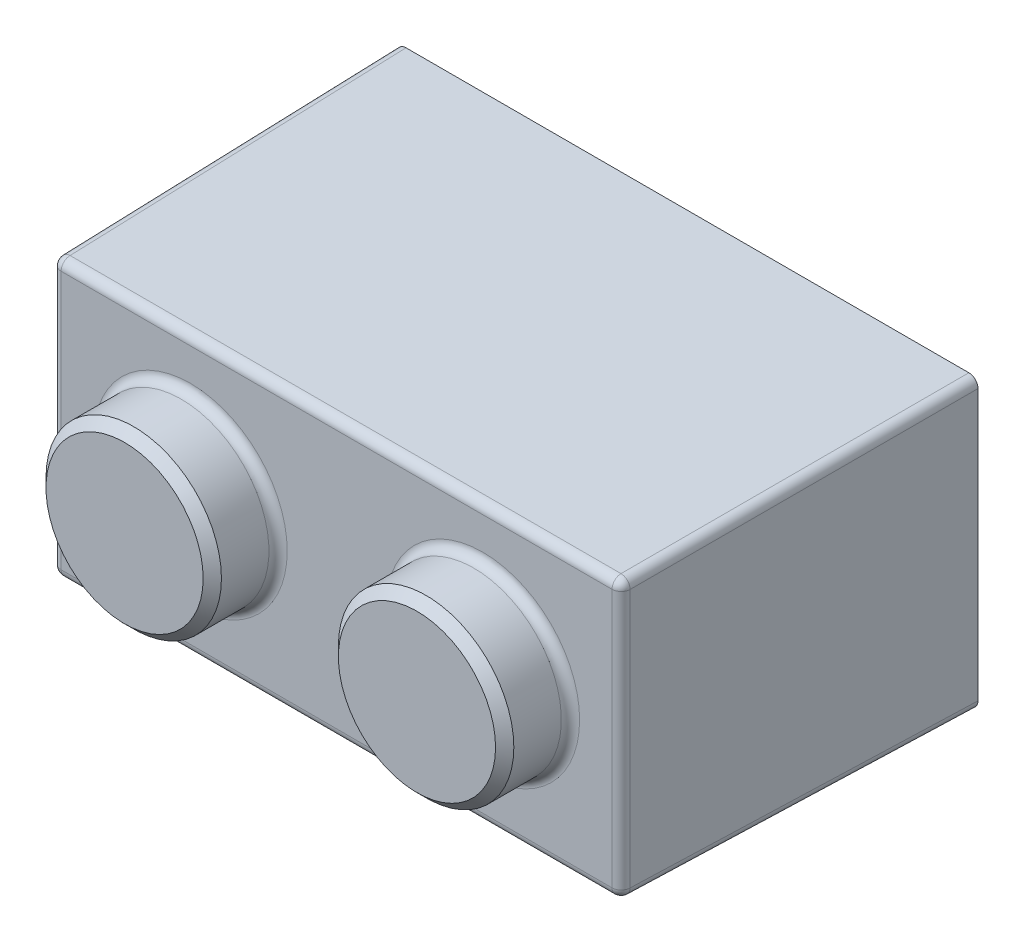
SolidWorks part; units mm, degrees
material "ABS"
ref_plane "Front" through (0, 0, 0) normal (0, 0, 1) x (1, 0, 0)
ref_plane "Top" through (0, 0, 0) normal (0, 1, 0) x (1, 0, 0)
ref_plane "Right" through (0, 0, 0) normal (1, 0, 0) x (0, 0, -1)
sketch "Sketch1" plane through (0, 0, 0) normal (0, 0, 1) x (1, 0, 0)
  line L1 (0, 0) -> (15.9, 0)
  line L2 (0, 0) -> (0, 7.9)
  line L3 (0, 7.9) -> (15.9, 7.9)
  line L4 (15.9, 0) -> (15.9, 7.9)
  dimension "D1" = 15.9
  dimension "D2" = 7.9
extrude "Main Body" add sketch "Sketch1" along normal blind 9.6 draft 1
sketch "Sketch2" plane through (0, 0, 9.6) normal (0, 0, 1) x (1, 0, 0)
  line L1 (0, 7.9) -> (0, 0) construction
  line L2 (0, 0) -> (15.9, 0) construction
  circle A0 centre (3.95, 3.95) radius 2.4
  dimension "D3" = 4.8
  dimension "D1" = 3.95
  dimension "D2" = 3.95
extrude "Post" add sketch "Sketch2" along normal blind 1.8
pattern_linear "Post LPattern1" count 2 spacing 8 along (1, 0, 0) of "Post"
shell "Shell1" thickness 1.2 removed face at (7.95, 3.95, 0)
fillet "Body Fillet" radius 0.25 10 edges at (7.95, 7.7324, 9.6) (15.7324, 3.95, 9.6) (7.95, 0.1676, 9.6) (0.1676, 3.95, 9.6) (1.55, 3.95, 9.6) (9.55, 3.95, 9.6) (15.8162, 7.8162, 4.8) (15.8162, 0.0838, 4.8) (0.0838, 7.8162, 4.8) (0.0838, 0.0838, 4.8)
chamfer "Post Chamfer" distance 0.25 angle 45 2 edges at (6.35, 3.95, 11.4) (14.35, 3.95, 11.4)
sketch "Sketch3" [suppressed] plane through (0, 0, 0) normal (0, 1, 0) x (1, 0, 0)
  line L1 (0, 0) -> (0.1633, -9.3544) construction
  line L3 (15.9563, -1.5437) -> (15.9563, -11.4)
  line L4 (0, 0) -> (0.1633, -9.3544) construction
  line L5 (0, 0) -> (0, -11.4) construction
  line L6 (0, -11.4) -> (7.9, -11.4) construction
  line L8 (7.9, -11.4) -> (15.9563, -11.4)
  line L9 (0.4132, -9.6) -> (15.4868, -9.6) construction
  line L10 (7.9, -9.6) -> (15.9563, -9.6) construction
  line L11 (7.9, -11.4) -> (7.9, -9.6)
  line L12 (7.9, -9.6) -> (15.9563, -1.5437)
  dimension "D1" = 11.4
  dimension "D2" = 7.9
  dimension "D3" = 45
extrude "Cut-Extrude1" [suppressed] cut sketch "Sketch3" along normal up to surface (7.7324 mm away) up to face at (7.95, 7.8184, 4.6772)
sketch "Sketch4" [suppressed] plane through (8.75, 0, 8.75) normal (0.7071, 0, 0.7071) x (0.7071, 0, -0.7071)
  line L4 (-0.8547, 0.1633) -> (9.7116, 0.0329)
  line L5 (10.0714, 0.2784) -> (10.0714, 7.6216)
  line L6 (9.7116, 7.8671) -> (-0.8547, 7.7367)
  line L7 (-1.2021, 7.4868) -> (-1.2021, 0.4132)
  line L8 (-0.8547, 0.1633) -> (9.7116, 0.0329)
  line L9 (10.0714, 0.2784) -> (10.0714, 7.6216)
  line L10 (9.7116, 7.8671) -> (-0.8547, 7.7367)
  line L11 (-1.2021, 7.4868) -> (-1.2021, 0.4132)
  ellipse E4 centre (9.7115, 0.2829) end of major axis (10.0714, 0.2742) minor radius 0.25 (9.7116, 0.0329) -> (10.0714, 0.2784) ccw
  ellipse E5 centre (9.7115, 7.6171) end of major axis (10.0714, 7.6258) minor radius 0.25 (10.0714, 7.6216) -> (9.7116, 7.8671) ccw
  ellipse E6 centre (-0.8485, 7.4868) end of major axis (-0.495, 7.4868) minor radius 0.25 (-0.8547, 7.7367) -> (-1.2021, 7.4868) ccw
  ellipse E7 centre (-0.8485, 0.4132) end of major axis (-1.2021, 0.4132) minor radius 0.25 (-1.2021, 0.4132) -> (-0.8547, 0.1633) ccw
  ellipse E8 centre (9.7115, 0.2829) end of major axis (10.0714, 0.2742) minor radius 0.25 (9.7116, 0.0329) -> (10.0714, 0.2784) ccw
  ellipse E9 centre (9.7115, 7.6171) end of major axis (10.0714, 7.6258) minor radius 0.25 (10.0714, 7.6216) -> (9.7116, 7.8671) ccw
  ellipse E10 centre (-0.8485, 7.4868) end of major axis (-0.495, 7.4868) minor radius 0.25 (-0.8547, 7.7367) -> (-1.2021, 7.4868) ccw
  ellipse E11 centre (-0.8485, 0.4132) end of major axis (-1.2021, 0.4132) minor radius 0.25 (-1.2021, 0.4132) -> (-0.8547, 0.1633) ccw
  dimension "D1" = 0
extrude "Boss-Extrude1" [suppressed] add sketch "Sketch4" against normal blind 1.2
fillet "Fillet1" [suppressed] radius 0.25
